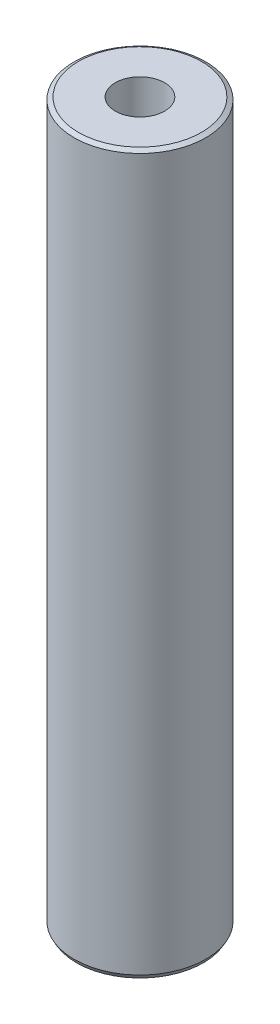
SolidWorks part; units mm, degrees
ref_plane "Front Plane" through (0, 0, 0) normal (0, 0, 1) x (1, 0, 0)
ref_plane "Top Plane" through (0, 0, 0) normal (0, 1, 0) x (1, 0, 0)
ref_plane "Right Plane" through (0, 0, 0) normal (1, 0, 0) x (0, 0, -1)
sketch "Sketch1" plane through (0, 0, 0) normal (0, 1, 0) x (1, 0, 0)
  circle A0 centre (0, 0) radius 55
  dimension "SHAFT_OD" = 110
extrude "Boss-Extrude1" add sketch "Sketch1" along normal blind 600
sketch "Sketch2" plane through (0, 0, 0) normal (0, 1, 0) x (1, 0, 0)
  circle A0 centre (0, 0) radius 20.6025
  dimension "BORE_D" = 41.2051
extrude "Cut-Extrude1" cut sketch "Sketch2" along normal through all
chamfer "Chamfer1" distance 2.0545 angle 60.367 2 edges at (0, 600, 55) (0, 0, 55) first distance on face at (0, 600, 55) first distance on face at (0, 0, 20.6025)
